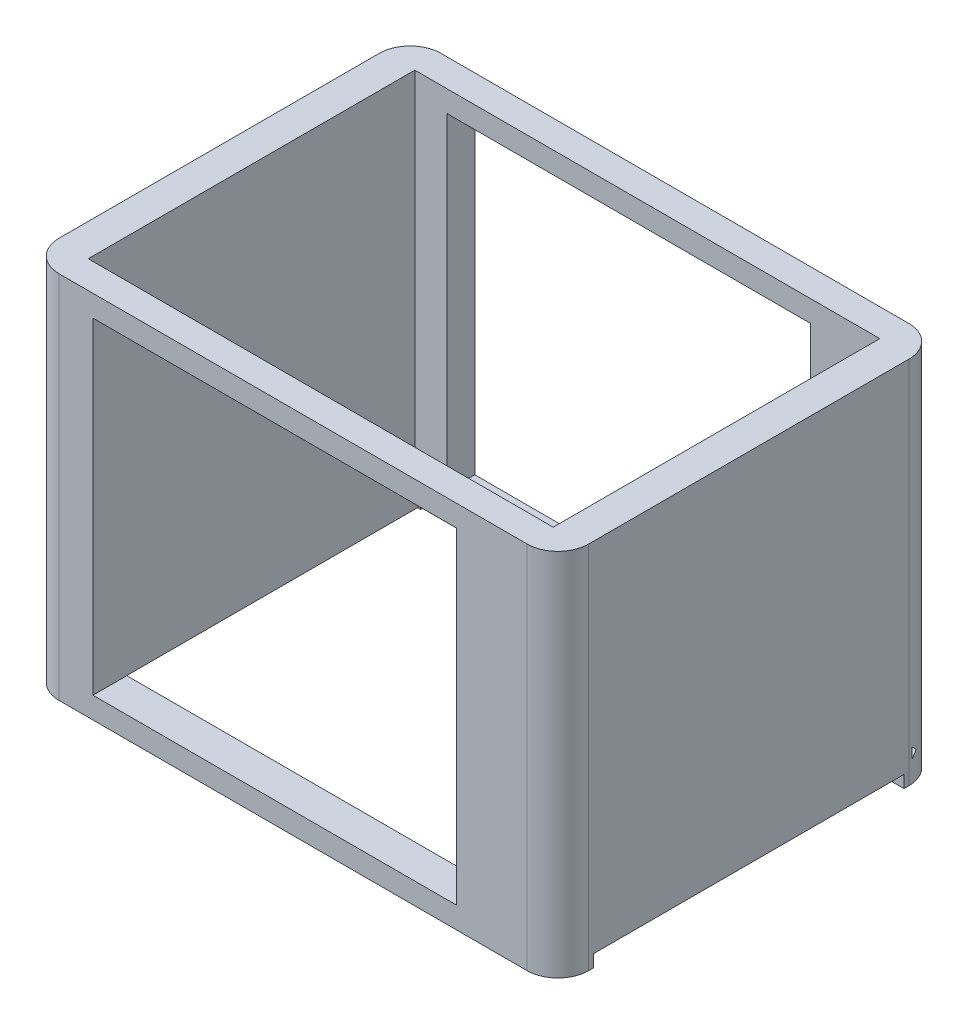
SolidWorks part; units mm, degrees
ref_plane "前视基准面" through (0, 0, 0) normal (0, 0, 1) x (1, 0, 0)
ref_plane "上视基准面" through (0, 0, 0) normal (0, 1, 0) x (1, 0, 0)
ref_plane "右视基准面" through (0, 0, 0) normal (1, 0, 0) x (0, 0, -1)
other "Configuration Table"
sketch "草图1" plane through (0, 0, 0) normal (0, 1, 0) x (1, 0, 0)
  line L1 (-43, -31) -> (43, -31)
  line L2 (-43, -31) -> (-43, 31)
  line L3 (-43, 31) -> (43, 31)
  line L4 (43, -31) -> (43, 31)
  line L5 (-43, -31) -> (43, 31) construction
  line L6 (-43, 31) -> (43, -31) construction
  line L7 (35.5, -25.5) -> (-35.5, -25.5)
  line L8 (35.5, -25.5) -> (35.5, 25.5)
  line L9 (35.5, 25.5) -> (-35.5, 25.5)
  line L10 (-35.5, -25.5) -> (-35.5, 25.5)
  line L11 (35.5, -25.5) -> (-35.5, 25.5) construction
  line L12 (35.5, 25.5) -> (-35.5, -25.5) construction
  point P0 (0, 0)
  point P5 (0, 0)
  dimension "D1" = 62
  dimension "D2" = 86
  dimension "D3" = 71
  dimension "D4" = 51
extrude "凸台-拉伸1" add sketch "草图1" along normal blind 60
sketch "草图2" plane through (0, 60, 0) normal (0, 1, 0) x (1, 0, 0)
  line L2 (-37.75, -26.515) -> (37.75, -26.515)
  line L3 (-37.75, -26.515) -> (-37.75, 26.515)
  line L4 (-37.75, 26.515) -> (37.75, 26.515)
  line L5 (37.75, -26.515) -> (37.75, 26.515)
  line L6 (-37.75, -26.515) -> (37.75, 26.515) construction
  line L7 (-37.75, 26.515) -> (37.75, -26.515) construction
  point P2 (0, 0)
  dimension "D1" = 53.03
  dimension "D2" = 75.5
extrude "切除-拉伸1" cut sketch "草图2" against normal blind 56.5
sketch "草图3" plane through (-37.75, 0, 0) normal (1, 0, 0) x (0, 0, -1)
  line L0 (26.515, 3.5) -> (-26.515, 60)
  line L1 (-26.515, 60) -> (-26.515, 3.5)
  line L2 (-26.515, 3.5) -> (26.515, 3.5)
extrude "凸台-拉伸2" add sketch "草图3" along normal blind 76
sketch "草图4" plane through (0, 0, 31) normal (0, 0, 1) x (1, 0, 0)
  line L0 (-43, 30) -> (43, 30) construction
  line L1 (-43, 60) -> (-43, 0) construction
  line L2 (43, 60) -> (43, 0) construction
  line L3 (43, 30) -> (0, 0) construction
  line L4 (0, 0) -> (0, 60) construction
  line L5 (-43, 60) -> (43, 60) construction
  line L7 (26.5, 3.485) -> (-32.5, 3.485)
  line L8 (26.5, 3.485) -> (26.5, 56.515)
  line L9 (26.5, 56.515) -> (-32.5, 56.515)
  line L10 (-32.5, 3.485) -> (-32.5, 56.515)
  line L11 (26.5, 3.485) -> (-32.5, 56.515) construction
  line L12 (26.5, 56.515) -> (-32.5, 3.485) construction
  point P12 (-3, 30)
  dimension "D1" = 59
  dimension "D2" = 53.03
  dimension "D3" = 10.5
extrude "切除-拉伸2" cut sketch "草图4" against normal through all
sketch "草图5" plane through (26.5, 0, 0) normal (-1, 0, 0) x (0, 0, 1)
  line L0 (-26.515, 3.5) -> (-27.3635, 4.3485)
  line L1 (-26.515, 56.515) -> (-26.515, 3.5) construction
  line L2 (-27.3635, 4.3485) -> (-26.515, 5.1971)
  line L3 (-26.515, 5.1971) -> (-26.515, 3.5)
  dimension "D1" = 45
  dimension "D2" = 1.2
  dimension "D3" = 90
extrude "切除-拉伸3" cut sketch "草图5" against normal through all both and the other way through all
sketch "草图7" plane through (0, 0, 0) normal (0, -1, 0) x (1, 0, 0)
  line L0 (-43, -31) -> (-43, 31) construction
  line L1 (43, -25.2) -> (-43, -25.2)
  line L2 (43, -25.2) -> (43, 25.2)
  line L3 (43, 25.2) -> (-43, 25.2)
  line L4 (-43, -25.2) -> (-43, 25.2)
  line L5 (43, -25.2) -> (-43, 25.2) construction
  line L6 (43, 25.2) -> (-43, -25.2) construction
  point P0 (0, 0)
  dimension "D1" = 50.4
extrude "切除-拉伸4" cut sketch "草图7" against normal blind 2
fillet "圆角1" radius 5 4 edges at (-43, 30, -31) (43, 30, -31) (43, 30, 31) (-43, 30, 31)
fillet "圆角2" radius 3 2 edges at (32.125, 5.1971, -26.515) (-35.125, 5.1971, -26.515)
